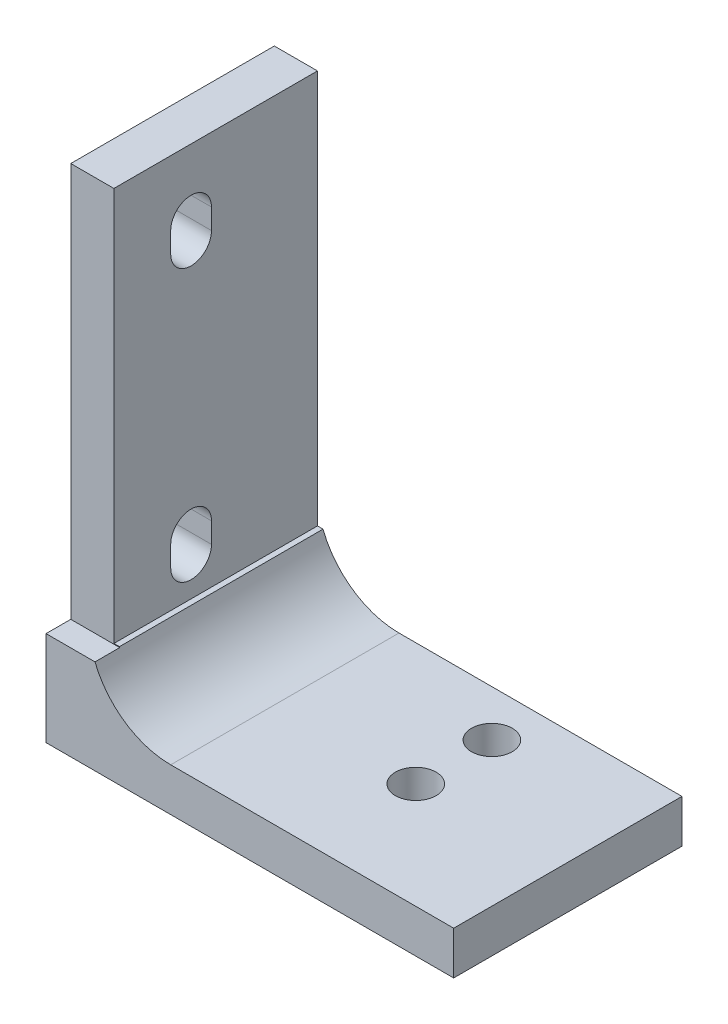
SolidWorks part; units mm, degrees
ref_plane "Front Plane" through (0, 0, 0) normal (0, 0, 1) x (1, 0, 0)
ref_plane "Top Plane" through (0, 0, 0) normal (0, 1, 0) x (1, 0, 0)
ref_plane "Right Plane" through (0, 0, 0) normal (1, 0, 0) x (0, 0, -1)
sketch "Sketch1" plane through (0, 0, 0) normal (0, 0, 1) x (1, 0, 0)
  line L0 (0, 0) -> (0, 36)
  line L1 (0, 0) -> (30, 0)
  line L2 (3.175, 3.175) -> (30, 3.175)
  line L3 (3.175, 3.175) -> (3.175, 36)
  line L4 (0, 36) -> (3.175, 36)
  line L5 (30, 0) -> (30, 3.175)
  dimension "D1" = 36
  dimension "D2" = 30
  dimension "D3" = 3.175
extrude "Boss-Extrude1" add sketch "Sketch1" along normal blind 8.4 and the other way blind 8.4
fillet "Fillet1" radius 6 1 edges at (3.175, 3.175, 0)
sketch "Sketch4" plane through (0, 0, 0) normal (-1, 0, 0) x (0, 0, 1)
  line L0 (0.9, 31.225) -> (0.9, 29.725) construction
  line L1 (2.4, 31.225) -> (2.4, 29.725)
  line L2 (-0.6, 31.225) -> (-0.6, 29.725)
  line L3 (0.9, 9.725) -> (0.9, 11.225) construction
  line L4 (-0.6, 9.725) -> (-0.6, 11.225)
  line L5 (2.4, 9.725) -> (2.4, 11.225)
  line L6 (8.4, 36) -> (8.4, 0) construction
  circle A2 centre (0.9, 10.475) radius 1.5 construction
  circle A3 centre (0.9, 30.475) radius 1.5 construction
  arc A4 (2.4, 31.225) -> (-0.6, 31.225) centre (0.9, 31.225) ccw
  arc A5 (-0.6, 29.725) -> (2.4, 29.725) centre (0.9, 29.725) ccw
  arc A6 (-0.6, 9.725) -> (2.4, 9.725) centre (0.9, 9.725) ccw
  arc A7 (2.4, 11.225) -> (-0.6, 11.225) centre (0.9, 11.225) ccw
  point P8 (0.9, 30.475)
  point P15 (0.9, 10.475)
  dimension "D1" = 20
  dimension "D2" = 10.475
  dimension "D3" = 7.5
extrude "Cut-Extrude2" cut sketch "Sketch4" against normal blind 10
sketch "Sketch3" plane through (0, 0, 0) normal (0, 0, 1) x (1, 0, 0)
  line L0 (3.175, 9.175) -> (3.175, 36) construction
  line L1 (3.175, 14.7374) -> (4.175, 14.7374)
  line L2 (3.175, 14.7374) -> (3.175, 7)
  line L3 (3.175, 7) -> (4.175, 7)
  line L4 (4.175, 14.7374) -> (4.175, 7)
  line L5 (0, 0) -> (30, 0) construction
  dimension "D1" = 7
  dimension "D2" = 1
extrude "Cut-Extrude1" cut sketch "Sketch3" against normal blind 10 and the other way blind 10
sketch "Sketch5" plane through (0, 0, 0) normal (0, -1, 0) x (1, 0, 0)
  circle A0 centre (19.41, 0.6) radius 1.5
  circle A1 centre (19.41, -5) radius 1.5
  dimension "D1" = 3
extrude "Cut-Extrude3" cut sketch "Sketch5" against normal blind 7
sketch "Sketch6" plane through (0, 0, 0) normal (-1, 0, 0) x (0, 0, 1)
  line L0 (-8.4, 0) -> (8.4, 0) construction
  line L1 (8.4, 36) -> (6.58, 36)
  line L2 (8.4, 36) -> (8.4, 6.95)
  line L3 (8.4, 6.95) -> (6.58, 6.95)
  line L4 (6.58, 36) -> (6.58, 6.95)
  dimension "D1" = 1.82
  dimension "D2" = 6.95
extrude "Cut-Extrude4" cut sketch "Sketch6" against normal blind 7
